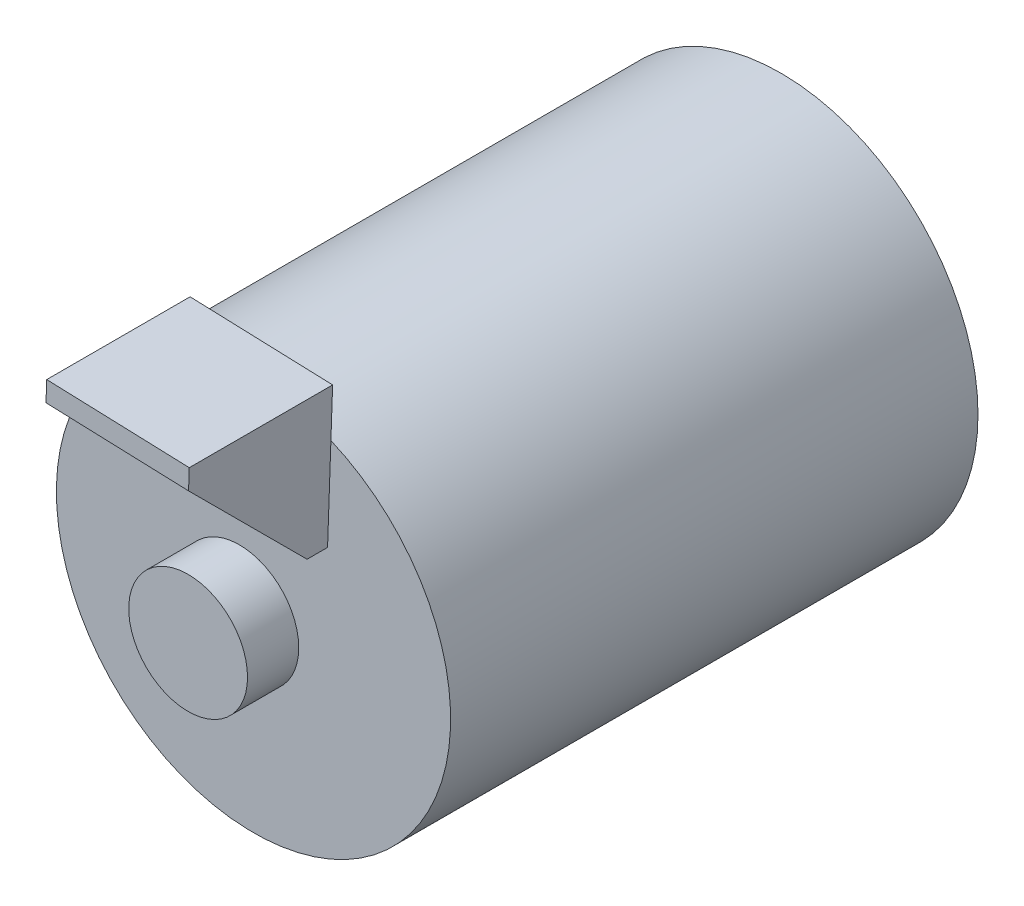
SolidWorks part; units mm, degrees
ref_plane "Front Plane" through (0, 0, 0) normal (0, 0, 1) x (1, 0, 0)
ref_plane "Top Plane" through (0, 0, 0) normal (0, 1, 0) x (1, 0, 0)
ref_plane "Right Plane" through (0, 0, 0) normal (1, 0, 0) x (0, 0, -1)
sketch "Sketch1" plane through (0, 0, 0) normal (0, 0, 1) x (1, 0, 0)
  circle A0 centre (0, 0) radius 38.5
  dimension "D1" = 77
extrude "Boss-Extrude1" add sketch "Sketch1" along normal blind 103
sketch "Sketch3" plane through (0, 0, 0) normal (1, 0, 0) x (0, 0, -1)
  line L0 (-103, 0) -> (-103, -6)
  line L1 (-103, 38.5) -> (-103, -38.5) construction
  line L2 (-103, -6) -> (-105.7672, -6)
  line L3 (-105.7672, -6) -> (-105.7672, -11.6)
  line L4 (-105.7672, -11.6) -> (-115.7672, -11.6)
  line L5 (-115.7672, -11.6) -> (-115.7672, 0)
  line L6 (-115.7672, 0) -> (-103, 0)
revolve "Revolve1" add sketch "Sketch3" angle 360 about L6
sketch "Sketch4" plane through (0, 0, 103) normal (0, 0, 1) x (1, 0, 0)
  line L0 (0.6173, 17.4891) -> (1.6049, 45.4717) construction
  line L1 (0.6173, 17.4891) -> (-13.374, 17.9829) construction
  line L2 (15.4538, 44.9829) -> (14.4661, 17.0003)
  line L3 (15.4538, 44.9829) -> (-12.3864, 45.9655)
  line L4 (14.4661, 17.0003) -> (-13.374, 17.9829)
  line L5 (-12.3864, 45.9655) -> (-13.374, 17.9829)
  line L6 (15.4538, 44.9829) -> (-13.374, 17.9829) construction
  line L7 (14.4661, 17.0003) -> (-12.3864, 45.9655) construction
  circle A0 centre (0, 0) radius 17.5
  point P7 (1.0399, 31.4829)
  circle M5 centre (0, 0) radius 38.5
  dimension "D1" = 35
extrude "Boss-Extrude2" add sketch "Sketch4" along normal blind 28 contours L5 L4 L2 M5 | L3 L5 L2 M5 region at (1.3779, 41.5105, 103) region at (0.908, 27.5714, 103)
sketch "Sketch5" plane through (-13.9913, 0.4938, 0) normal (-0.9994, 0.0353, 0) x (0, 0, 1)
  line L0 (131, 45.5) -> (131, 41.5) construction
  line L1 (131, 45.5) -> (131, 17.5) construction
  line L2 (103, 17.5) -> (107, 17.5) construction
  line L3 (131, 17.5) -> (103, 17.5) construction
  line L4 (107, 17.5) -> (131, 41.5)
  line L5 (131, 41.5) -> (131, 17.5)
  line L6 (131, 17.5) -> (107, 17.5)
extrude "Cut-Extrude1" cut sketch "Sketch5" against normal blind 28 contours L4 L5 L6
shell "Shell2" thickness 4 removed face at (0.9693, 29.4842, 119) removed face at (1.4631, 43.4754, 131)
sketch "Sketch6" plane through (0, 0, 0) normal (0, 0, -1) x (-1, 0, 0)
  circle A0 centre (0, 0) radius 5
extrude "Boss-Extrude3" add sketch "Sketch6" along normal blind 12
